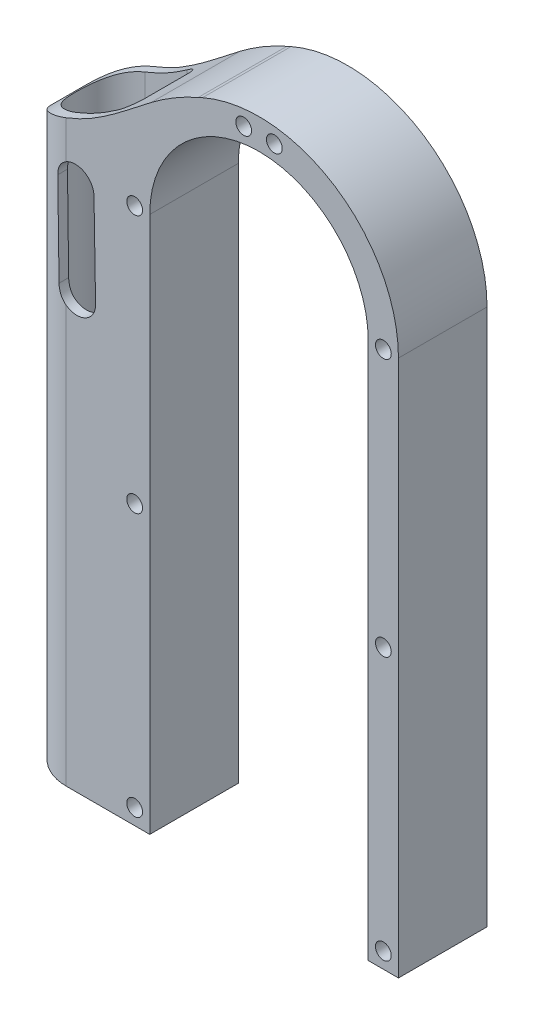
SolidWorks part; units mm, degrees
ref_plane "Front Plane" through (0, 0, 0) normal (0, 0, 1) x (1, 0, 0)
ref_plane "Top Plane" through (0, 0, 0) normal (0, 1, 0) x (1, 0, 0)
ref_plane "Right Plane" through (0, 0, 0) normal (1, 0, 0) x (0, 0, -1)
sketch "Sketch1" plane through (0, 0, 0) normal (0, 0, 1) x (1, 0, 0)
  line L0 (-179.0854, -18.7892) -> (-179.0854, 212.1883)
  line L1 (-119.0854, -18.7892) -> (-119.0854, 212.1883)
  line L2 (-172.5854, -18.7892) -> (-172.5854, 212.1883)
  line L3 (-125.5854, -18.7892) -> (-125.5854, 212.1883)
  arc A0 (-119.0854, 212.1883) -> (-179.0854, 212.1883) centre (-149.0854, 212.1883) ccw
  arc A1 (-179.0854, -18.7892) -> (-119.0854, -18.7892) centre (-149.0854, -18.7892) ccw
  arc A2 (-125.5854, 212.1883) -> (-172.5854, 212.1883) centre (-149.0854, 212.1883) ccw
  arc A3 (-172.5854, -18.7892) -> (-125.5854, -18.7892) centre (-149.0854, -18.7892) ccw
  dimension "D1" = 47
  dimension "D2" = 47
  dimension "D3" = 53.5
extrude "Boss-Extrude1" add sketch "Sketch1" along normal blind 19.05
sketch "Sketch2" plane through (0, 0, 19.05) normal (0, 0, 1) x (1, 0, 0)
  line L0 (-175.8354, 212.1883) -> (-175.8354, -18.7892) construction
  line L1 (-122.3354, 212.1883) -> (-122.3354, -18.7892) construction
  line L2 (-149.0854, 242.1883) -> (-149.0854, 231.9427) construction
  line L3 (-149.0854, -48.7892) -> (-149.0854, -37.4384) construction
  line L4 (-179.0854, 96.6996) -> (-118.7003, 96.6996) construction
  line L5 (-179.0854, 212.1883) -> (-179.0854, -18.7892) construction
  arc A0 (-122.3354, 212.1883) -> (-175.8354, 212.1883) centre (-149.0854, 212.1883) ccw construction
  arc A1 (-119.0854, 212.1883) -> (-179.0854, 212.1883) centre (-149.0854, 212.1883) ccw construction
  arc A2 (-125.5854, 212.1883) -> (-172.5854, 212.1883) centre (-149.0854, 212.1883) ccw construction
  arc A3 (-175.8354, -18.7892) -> (-122.3354, -18.7892) centre (-149.0854, -18.7892) ccw construction
  arc A4 (-179.0854, -18.7892) -> (-119.0854, -18.7892) centre (-149.0854, -18.7892) ccw construction
  circle A5 centre (-145.7854, 238.734) radius 1.7
  circle A7 centre (-122.3354, 212.1883) radius 1.7
  circle A8 centre (-152.4854, -45.3222) radius 1.7
  circle A9 centre (-168.0005, -37.7043) radius 1.7
  circle A10 centre (-175.8354, -18.7892) radius 1.7
  circle A11 centre (-175.8354, 212.1883) radius 1.7
  circle A13 centre (-145.6854, -45.3222) radius 1.7
  circle A14 centre (-175.8354, 100.0996) radius 1.7
  circle A15 centre (-175.8354, 93.2996) radius 1.7
  circle A16 centre (-122.3354, 100.0996) radius 1.7
  circle A17 centre (-122.3354, 93.2996) radius 1.7
  circle A19 centre (-122.3354, -18.7892) radius 1.7
  circle A20 centre (-130.1703, -37.7043) radius 1.7
  circle A25 centre (-175.8354, 156.6996) radius 1.7
  circle A26 centre (-122.3354, 156.6996) radius 1.7
  circle A29 centre (-175.8354, 66.6996) radius 1.7
  circle A30 centre (-122.3354, 66.6996) radius 1.7
  circle A31 centre (-175.8354, 36.6996) radius 1.7
  circle A32 centre (-122.3354, 36.6996) radius 1.7
  circle A33 centre (-175.8354, 6.6996) radius 1.7
  circle A34 centre (-122.3354, 6.6996) radius 1.7
  circle A35 centre (-152.3854, 238.734) radius 1.7
  point P35 (-149.0854, 212.1883)
  point P52 (-149.0854, -18.7892)
  dimension "D1" = 3.25
  dimension "D2" = 3.25
  dimension "D3" = 3.25
  dimension "D4" = 3.4
  dimension "D6" = 3.4
  dimension "D8" = 3.4
  dimension "D9" = 3.4
  dimension "D5" = 3.4
  dimension "D12" = 3.3
  dimension "D13" = 3.3
  dimension "D14" = 3.4
  dimension "D7" = 3.4
  dimension "D16" = 3.4
  dimension "D17" = 3.4
  dimension "D18" = 3.4
  dimension "D19" = 3.4
  dimension "D20" = 3.4
  dimension "D10" = 3.4
  dimension "D11" = 3.4
  dimension "D21" = 3.4
  dimension "D22" = 3.4
  dimension "D25" = 3.4
  dimension "D26" = 3.4
  dimension "D15" = 3.4
  dimension "D23" = 3.4
extrude "Cut-Extrude1" cut sketch "Sketch2" against normal through all
sketch "Sketch3" plane through (0, 0, 19.05) normal (0, 0, 1) x (1, 0, 0)
  line L1 (-149.0854, 96.6996) -> (-100.1673, 96.6996)
  line L2 (-100.1673, 96.6996) -> (-100.1673, -59.1719)
  line L3 (-100.1673, -59.1719) -> (-212.5278, -59.1719)
  line L4 (-212.5278, -59.1719) -> (-212.5278, 96.6996)
  line L5 (-149.0854, 96.6996) -> (-212.5278, 96.6996)
extrude "Cut-Extrude2" cut sketch "Sketch3" against normal through all
sketch "Sketch4" plane through (0, 96.6996, 0) normal (0, -1, 0) x (1, 0, 0)
  line L0 (-172.5854, 9.525) -> (-206.4878, 9.525) construction
  line L1 (-172.5854, 19.05) -> (-172.5854, 0) construction
  line L2 (-172.5854, 0) -> (-125.5854, 0) construction
  line L3 (-179.0854, 19.05) -> (-196.6522, 19.05)
  line L4 (-179.0854, 0) -> (-196.6522, 0)
  line L6 (-179.0854, 19.05) -> (-179.0854, 0)
  arc A1 (-196.6522, 19.05) -> (-196.6522, 0) centre (-187.0854, 9.525) ccw
  dimension "D1" = 27
extrude "Boss-Extrude2" add sketch "Sketch4" against normal blind 135
sketch "Sketch5" plane through (0, 0, 19.05) normal (0, 0, 1) x (1, 0, 0)
  line L0 (-179.0854, 231.6996) -> (-179.0854, 212.1883) construction
  line L1 (-179.0854, 231.6996) -> (-179.0854, 212.1883)
  line L2 (-179.0854, 231.6996) -> (-161.2502, 239.6113)
  arc A0 (-119.0854, 212.1883) -> (-179.0854, 212.1883) centre (-149.0854, 212.1883) ccw construction
  arc A1 (-161.2502, 239.6113) -> (-179.0854, 212.1883) centre (-149.0854, 212.1883) ccw
extrude "Boss-Extrude3" add sketch "Sketch5" against normal up to surface (19.05 mm away) up to face at (-120.6354, 100.0996, 0)
sketch "Sketch6" plane through (0, 0, 19.05) normal (0, 0, 1) x (1, 0, 0)
  line L0 (-200.5854, 231.6996) -> (-200.5854, 96.6996) construction
  line L1 (-196.6522, 231.6996) -> (-196.6522, 96.6996) construction
  line L2 (-166.9483, 237.0836) -> (-200.5854, 237.0836)
  line L3 (-200.5854, 237.0836) -> (-200.5854, 215.1698)
  line L4 (-161.2502, 239.6113) -> (-179.0854, 231.6996) construction
  spline S0 degree 3 poles (-166.9483, 237.0836) (-174.0803, 232.2647) (-185.6194, 221.2567) (-196.5216, 219.6744) (-200.5854, 215.1698) knots 0 0 0 0 0.585488 1 1 1 1
extrude "Cut-Extrude4" cut sketch "Sketch6" against normal through all
sketch "Sketch7" plane through (0, 96.6996, 0) normal (0, -1, 0) x (1, 0, 0)
  line L0 (-200.5854, 9.525) -> (-198.0854, 9.525) construction
  line L3 (-190.5854, 9.525) -> (-148.7441, 9.525) construction
  line L4 (-190.5854, 17.025) -> (-178.5854, 17.025)
  line L6 (-190.5854, 2.025) -> (-178.5854, 2.025)
  line L7 (-178.5854, 17.025) -> (-178.5854, 2.025)
  arc A3 (-196.6522, 19.05) -> (-196.6522, 0) centre (-187.0854, 9.525) ccw construction
  arc A4 (-190.5854, 17.025) -> (-190.5854, 2.025) centre (-190.5854, 9.525) ccw
  dimension "D1" = 15
  dimension "D2" = 3.5
  dimension "D3" = 22
extrude "Cut-Extrude5" cut sketch "Sketch7" against normal through all
sketch "Sketch8" plane through (0, 0, 19.05) normal (0, 0, 1) x (1, 0, 0)
  line L0 (-188.578, 209.5552) -> (-188.2406, 189.558) construction
  line L2 (-184.5786, 209.6226) -> (-184.2412, 189.6255)
  line L3 (-192.5774, 209.4877) -> (-192.2401, 189.4905)
  arc A0 (-184.5786, 209.6226) -> (-192.5774, 209.4877) centre (-188.578, 209.5552) ccw
  arc A1 (-192.2401, 189.4905) -> (-184.2412, 189.6255) centre (-188.2406, 189.558) ccw
  point P4 (-188.4093, 199.5566)
  dimension "D1" = 4
  dimension "D2" = 20
  dimension "D3" = 12
extrude "Cut-Extrude6" cut sketch "Sketch8" against normal blind 7
fillet "Fillet1" radius 50 1 edges at (-166.9483, 237.0836, 9.525)
fillet "Fillet2" radius 10 2 edges at (-196.6522, 157.566, 0) (-196.6522, 157.566, 19.05)
fillet "Fillet3" radius 3 2 edges at (-178.5854, 162.5123, 17.025) (-178.5854, 162.5123, 2.025)
